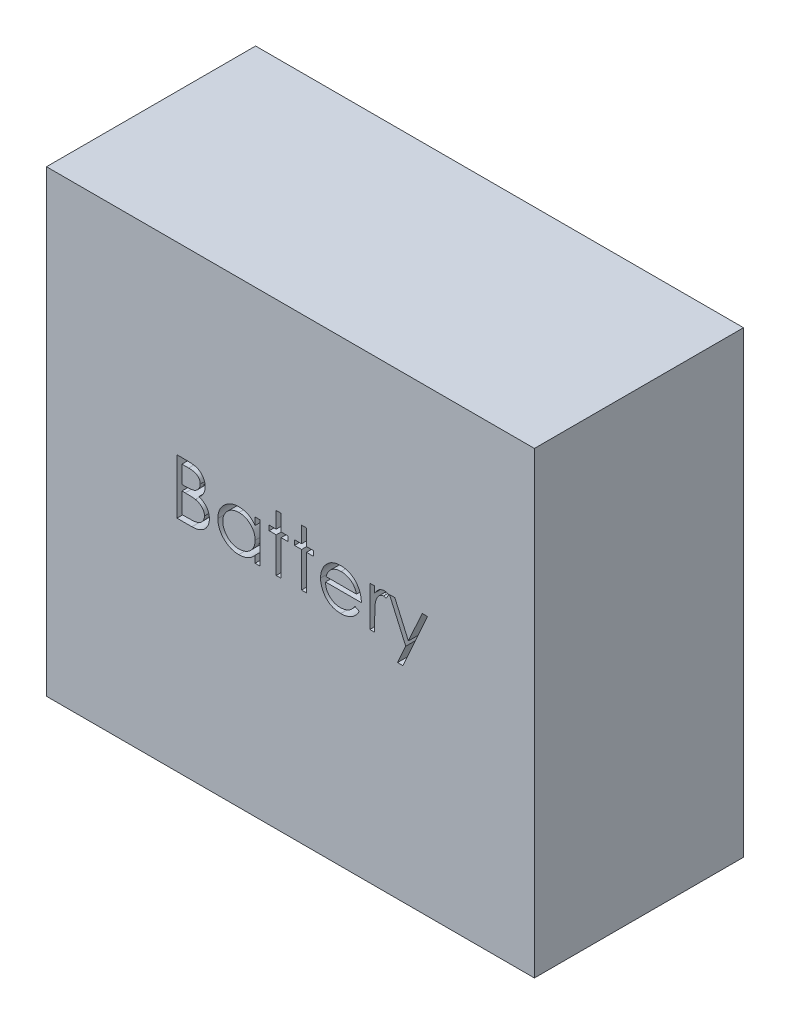
SolidWorks part; units mm, degrees
ref_plane "Front Plane" through (0, 0, 0) normal (0, 0, 1) x (1, 0, 0)
ref_plane "Top Plane" through (0, 0, 0) normal (0, 1, 0) x (1, 0, 0)
ref_plane "Right Plane" through (0, 0, 0) normal (1, 0, 0) x (0, 0, -1)
sketch "Sketch1" plane through (0, 0, 0) normal (0, 1, 0) x (1, 0, 0)
  line L1 (88.9, -38.1) -> (-88.9, -38.1)
  line L2 (88.9, -38.1) -> (88.9, 38.1)
  line L3 (88.9, 38.1) -> (-88.9, 38.1)
  line L4 (-88.9, -38.1) -> (-88.9, 38.1)
  line L5 (88.9, -38.1) -> (-88.9, 38.1) construction
  line L6 (88.9, 38.1) -> (-88.9, -38.1) construction
  point P0 (0, 0)
  dimension "D1" = 177.8
  dimension "D2" = 76.2
extrude "Boss-Extrude1" add sketch "Sketch1" along normal blind 167.13
sketch "Sketch2" plane through (0, 0, 38.1) normal (0, 0, 1) x (1, 0, 0)
  line L0 (-88.9, 167.13) -> (-88.9, 0) construction
  text T0 "Battery" font "Century Gothic" height 20
  point P2 (0, 0)
  point P3 (0, 0)
  point P4 (-59.1938, 80)
  dimension "D1" = 80
  dimension "D2" = 45
extrude "Cut-Extrude1" cut sketch "Sketch2" against normal blind 20
